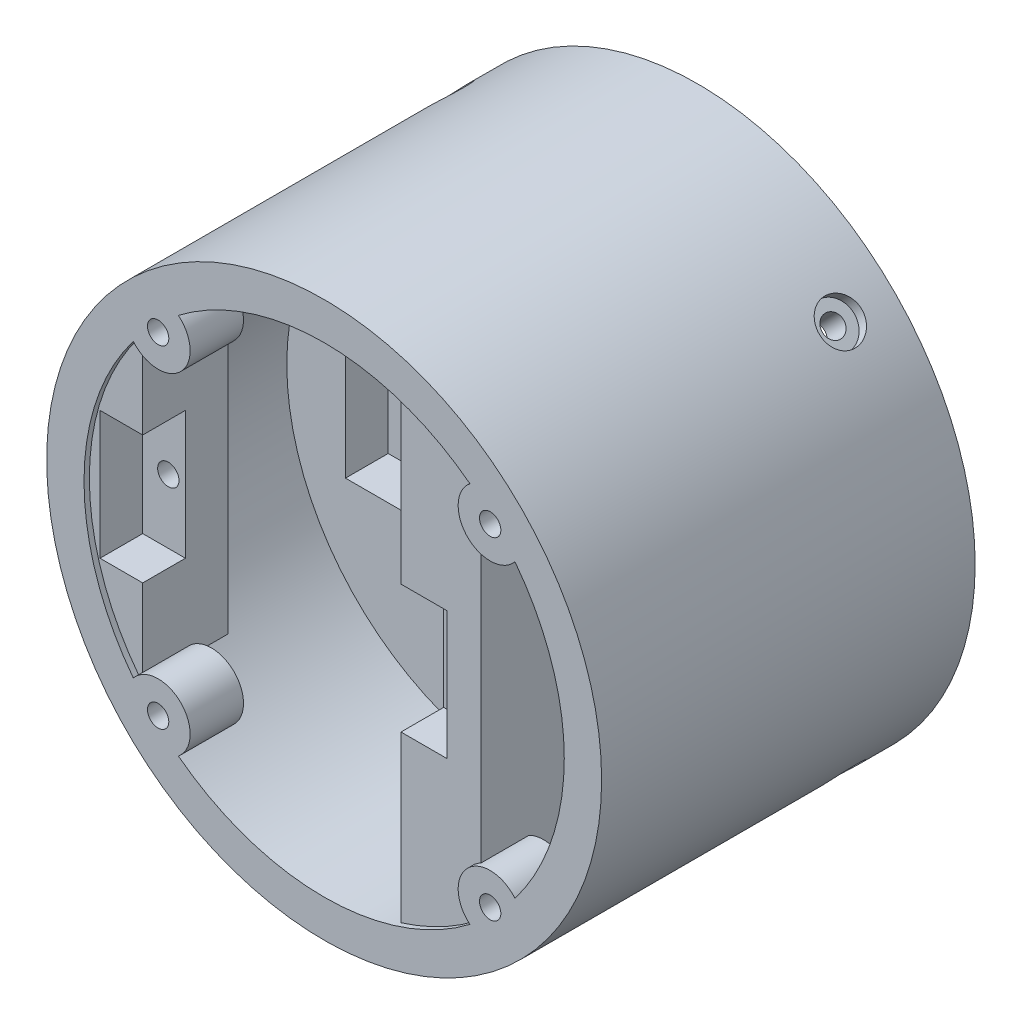
SolidWorks part; units mm, degrees
material "ABS"
ref_plane "Спереди" through (0, 0, 0) normal (0, 0, 1) x (1, 0, 0)
ref_plane "Сверху" through (0, 0, 0) normal (0, 1, 0) x (1, 0, 0)
ref_plane "Справа" through (0, 0, 0) normal (1, 0, 0) x (0, 0, -1)
sketch "Эскиз1" plane through (0, 0, 0) normal (0, 0, 1) x (1, 0, 0)
  circle A1 centre (0, 0) radius 26
  dimension "D1" = 52
extrude "Бобышка-Вытянуть1" add sketch "Эскиз1" along normal blind 35
sketch "Эскиз3" plane through (0, 0, 0) normal (0, 0, -1) x (-1, 0, 0)
  circle A0 centre (0, 0) radius 22.5
  dimension "D1" = 45
extrude "Вырез-Вытянуть1" cut sketch "Эскиз3" against normal blind 11 contours A0
sketch "Эскиз10" plane through (0, 0, 11) normal (0, 0, -1) x (-1, 0, 0)
  circle A0 centre (0, 0) radius 15
  dimension "D1" = 30
sketch "Эскиз4" plane through (0, 0, 35) normal (0, 0, 1) x (1, 0, 0)
  circle A0 centre (0, 0) radius 22.5
  dimension "D1" = 45
extrude "Вырез-Вытянуть2" cut sketch "Эскиз4" against normal offset from surface (19 mm away) 5 up to face at (-22.5, 0, 11)
sketch "Эскиз13" plane through (0, 0, 16) normal (0, 0, 1) x (1, 0, 0)
  line L0 (0, 26) -> (0, -26) construction
  line L1 (-26, 0) -> (26, 0) construction
  line L3 (-17, 6.5) -> (7, 6.5)
  line L4 (-17, 6.5) -> (-17, -6.5)
  line L5 (-17, -6.5) -> (7, -6.5)
  line L6 (7, 6.5) -> (7, -6.5)
  circle A0 centre (0, 0) radius 26 construction
  point P11 (-17, 0)
  point P13 (-5, 6.5)
  dimension "D1" = 13
  dimension "D2" = 24
  dimension "D3" = 5
extrude "Вырез-Вытянуть3" cut sketch "Эскиз13" against normal blind 4
sketch "Эскиз12" plane through (0, 0, 35) normal (0, 0, 1) x (1, 0, 0)
  line L0 (0, 26) -> (0, -26) construction
  line L1 (0, 0) -> (28.1458, 16.25) construction
  line L2 (-26, 0) -> (32.5, 0) construction
  line L5 (19.4856, 11.25) -> (22.5167, 13)
  line L6 (19.4856, -11.25) -> (22.5167, -13)
  circle A0 centre (0, 0) radius 26 construction
  arc A4 (19.4856, -11.25) -> (19.4856, 11.25) centre (0, 0) ccw
  arc A6 (22.5167, -13) -> (22.5167, 13) centre (0, 0) ccw
  dimension "D1" = 30
ref_plane "Плоскость2" through (0, 0, 26.5) normal (0, 0, 1) x (1, 0, 0)
sketch "Эскиз14" plane through (0, 0, 26.5) normal (0, 0, 1) x (1, 0, 0)
  line L1 (7, 0) -> (-46.5151, 0) construction
  line L2 (7, -6.5) -> (7, 6.5) construction
  line L3 (-17.5, -28.5313) -> (-17.5, 17.8536) construction
  line L6 (7, 0) -> (57.6607, 0) construction
  line L8 (14.2, -44.5711) -> (14.2, 20) construction
  line L10 (14.2, -20.5757) -> (14.2, 20.5757)
  line L13 (-17.5, -17.8536) -> (-17.5, 17.8536)
  line L15 (6.7, -24.0855) -> (6.7, 24.0855)
  line L16 (0, -28.5313) -> (0, 28.5313) construction
  arc A4 (-17.5, 17.8536) -> (-17.5, -17.8536) centre (0, 0) ccw
  arc A5 (14.2, 20.5757) -> (6.7, 24.0855) centre (0, 0) ccw
  arc A6 (6.7, -24.0855) -> (14.2, -20.5757) centre (0, 0) ccw
  point P11 (-17.5, 0)
  point P18 (7, 0)
  point P22 (14.2, 0)
  point P27 (14.2, 0)
  point P29 (-17.5, 0)
  point P33 (7.5, 0)
  point P34 (6.7, 0)
  point P35 (0, 0)
  dimension "D1" = 17.5
  dimension "D4" = 6.7
extrude "Бобышка-Вытянуть2" add sketch "Эскиз14" along normal blind 8
sketch "Эскиз15" plane through (0, 0, 34.5) normal (0, 0, 1) x (1, 0, 0)
  line L0 (43.3889, 0) -> (-43.3889, 0) construction
  line L1 (0, 36.1435) -> (0, -36.1435) construction
  line L2 (-21.5, 29.8665) -> (-21.5, -29.8665) construction
  line L3 (11, 32.0712) -> (11, -32.0712) construction
  line L4 (-17.5, 23.7559) -> (-17.5, -23.2484) construction
  line L5 (-21.5, -6) -> (-21.5, 6)
  line L6 (-21.5, 6) -> (-17.5, 6)
  line L7 (6.7, 41.39) -> (6.7, -19.4927) construction
  line L8 (6.7, 21.4793) -> (6.7, -21.4793) construction
  line L9 (11, -6) -> (11, 6)
  line L10 (11, 6) -> (6.7, 6)
  line L11 (-17.5, 6) -> (-17.5, -6)
  line L12 (6.7, 6) -> (6.7, -6)
  line L13 (11, -6) -> (6.7, -6)
  line L14 (-21.5, -6) -> (-17.5, -6)
  point P4 (0, 0)
  point P8 (0, 0)
  point P11 (-21.5, 0)
  point P14 (11, 0)
  point P19 (-17.5, 0.2537)
  point P24 (6.7, 10.9487)
  point P30 (6.7, 0)
  point P31 (11, 0)
  point P32 (-17.5, 0)
  point P33 (-21.5, 0)
  dimension "D1" = 21.5
  dimension "D2" = 11
  dimension "D3" = 6
  dimension "D4" = 6
extrude "Вырез-Вытянуть5" cut sketch "Эскиз15" along direction (0, 0, 1) on the side against the normal offset from surface (4 mm away) 18.5 up to face at (-5, 0, 12)
sketch "Эскиз17" plane through (0, 0, 30.5) normal (0, 0, 1) x (1, 0, 0)
  circle A1 centre (-19.1, 0) radius 1
  circle A2 centre (8.6, 0) radius 1
extrude "Вырез-Вытянуть6" cut sketch "Эскиз17" along direction (0, 0, 1) on the side against the normal up to surface (4 mm away) up to face at (10.5461, 0, 26.5)
sketch "Эскиз20" plane through (0, 0, 35) normal (0, 0, 1) x (1, 0, 0)
  line L0 (-57.2124, 0) -> (57.2124, 0) construction
  line L1 (0, 34.3681) -> (0, -34.3681) construction
  line L2 (0, 0) -> (-44.2288, 44.2288) construction
  circle A0 centre (0, 0) radius 22 construction
  circle A2 centre (0, 0) radius 26 construction
  circle A3 centre (-15.5563, 15.5563) radius 3
  circle A4 centre (15.5563, 15.5563) radius 3
  circle A5 centre (15.5563, -15.5563) radius 3
  circle A6 centre (-15.5563, -15.5563) radius 3
  point P3 (-15.5563, 15.5563)
  point P8 (0, 0)
  point P12 (0, 0)
  point P23 (0, 0)
  point P27 (0, 0)
  dimension "D2" = 52
  dimension "D3" = 22
  dimension "D1" = 6
  dimension "D4" = 4
extrude "Бобышка-Вытянуть3" add sketch "Эскиз20" against normal blind 5
sketch "Эскиз21" plane through (0, 0, 35) normal (0, 0, 1) x (1, 0, 0)
  circle A4 centre (-15.5563, 15.5563) radius 1
  circle A11 centre (15.5563, 15.5563) radius 1
  circle A12 centre (15.5563, -15.5563) radius 1
  circle A13 centre (-15.5563, -15.5563) radius 1
  point P11 (-0.7071, 0)
  point P12 (0, 0)
  point P14 (0.7071, 0)
  point P15 (0, 0)
  dimension "D1" = 2
  dimension "D2" = 4
extrude "Вырез-Вытянуть9" cut sketch "Эскиз21" against normal blind 5
sketch "Эскиз24" plane through (0, 0, 16) normal (0, 0, 1) x (1, 0, 0)
  line L0 (7, -6.5) -> (7, 6.5) construction
  line L1 (11, 4) -> (13.5, 4)
  line L2 (11, 4) -> (11, -4)
  line L3 (11, -4) -> (13.5, -4)
  line L4 (13.5, 4) -> (13.5, -4)
  point P7 (11, 0)
  point P10 (7, 0)
  dimension "D1" = 2.5
  dimension "D2" = 8
  dimension "D4" = 4
extrude "Вырез-Вытянуть12" cut sketch "Эскиз24" against normal up to surface (5 mm away) up to face at (-22.5, 0, 11)
ref_plane "Плоскость3" through (-18.3848, -18.3848, 35) normal (-0.7071, -0.7071, 0) x (-0.7071, 0.7071, 0)
sketch "Эскиз25" plane through (-18.3848, -18.3848, 35) normal (-0.7071, -0.7071, 0) x (-0.7071, 0.7071, 0)
  line L0 (0, 0) -> (0, 35) construction
  circle A0 centre (0, 30) radius 2
  dimension "D1" = 4
  dimension "D2" = 5
extrude "Вырез-Вытянуть13" cut sketch "Эскиз25" against normal blind 1
sketch "Эскиз26" plane through (-17.6777, -17.6777, 0) normal (-0.7071, -0.7071, 0) x (0, 0, 1)
  circle A0 centre (5, 0) radius 1
  dimension "D1" = 2
extrude "Вырез-Вытянуть14" cut sketch "Эскиз26" against normal through all
pattern_circular "Круговой массив1" count 4 over 360 about axis through (0, 0, 35) along (0, 0, -1) of "Вырез-Вытянуть14", "Вырез-Вытянуть13"
chamfer "Фаска1" distance 0.5 angle 45 1 edges at (-22.5, 0, 0)
